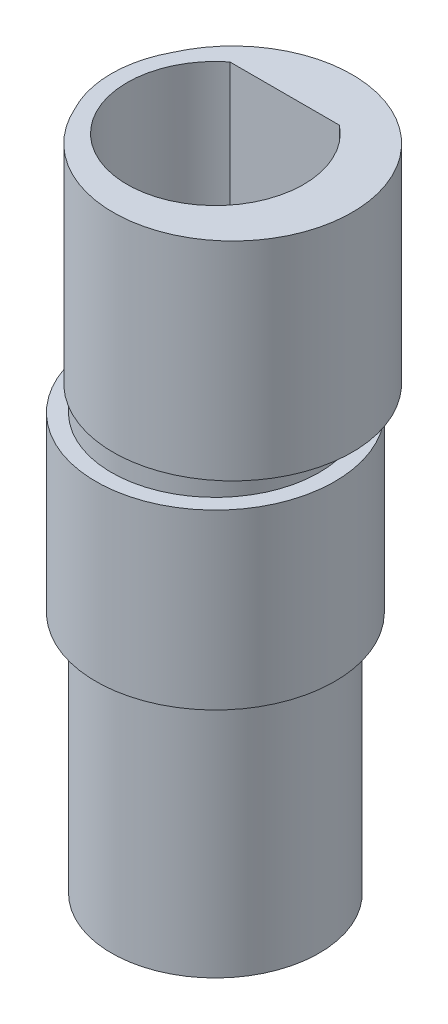
SolidWorks part; units mm, degrees
ref_plane "Front Plane" through (0, 0, 0) normal (0, 0, 1) x (1, 0, 0)
ref_plane "Top Plane" through (0, 0, 0) normal (0, 1, 0) x (1, 0, 0)
ref_plane "Right Plane" through (0, 0, 0) normal (1, 0, 0) x (0, 0, -1)
sketch "Sketch1" plane through (0, 0, 0) normal (0, 1, 0) x (1, 0, 0)
  circle A0 centre (0, 0) radius 3.45
  dimension "D1" = 6.9
extrude "Boss-Extrude1" add sketch "Sketch1" along normal blind 6
sketch "Sketch2" plane through (0, -4.98, 0) normal (0, -1, 0) x (1, 0, 0)
  line L0 (0, 0) -> (-0.5, 0) construction
  circle A0 centre (-0.5, 0) radius 3.45
  dimension "D1" = 6.9
extrude "Boss-Extrude2" add sketch "Sketch2" against normal blind 4 and the other way blind 1
sketch "Sketch3" plane through (0, 6, 0) normal (0, 1, 0) x (1, 0, 0)
  circle A0 centre (-0.5, 0) radius 3
  dimension "D1" = 6
extrude "Boss-Extrude4" add sketch "Sketch3" against normal blind 22
sketch "Sketch4" plane through (0, -16, 0) normal (0, -1, 0) x (1, 0, 0)
  line L0 (0, 0) -> (-0.5, 0)
  circle A0 centre (-0.5, 0) radius 2.55
  dimension "D1" = 5.1
extrude "Cut-Extrude1" cut sketch "Sketch4" against normal through all contours A0
sketch "Sketch5" plane through (0, 6, 0) normal (0, 1, 0) x (1, 0, 0)
  line L2 (1.0819, 2) -> (-2.0819, 2)
  circle A0 centre (-0.5, 0) radius 2.55 construction
  circle A1 centre (-0.5, 0) radius 2.55
  circle M3 centre (-0.5, 0) radius 2.55
extrude "Boss-Extrude5" add sketch "Sketch5" against normal blind 12.8 contours L2 M3 region at (-0.5, 6, -2.2222)
sketch "Sketch6" plane through (0, -16, 0) normal (0, -1, 0) x (1, 0, 0)
  circle A0 centre (-0.5, 0) radius 3
  circle A1 centre (-0.5, 0) radius 2.55
extrude "Cut-Extrude2" cut sketch "Sketch6" against normal blind 3
